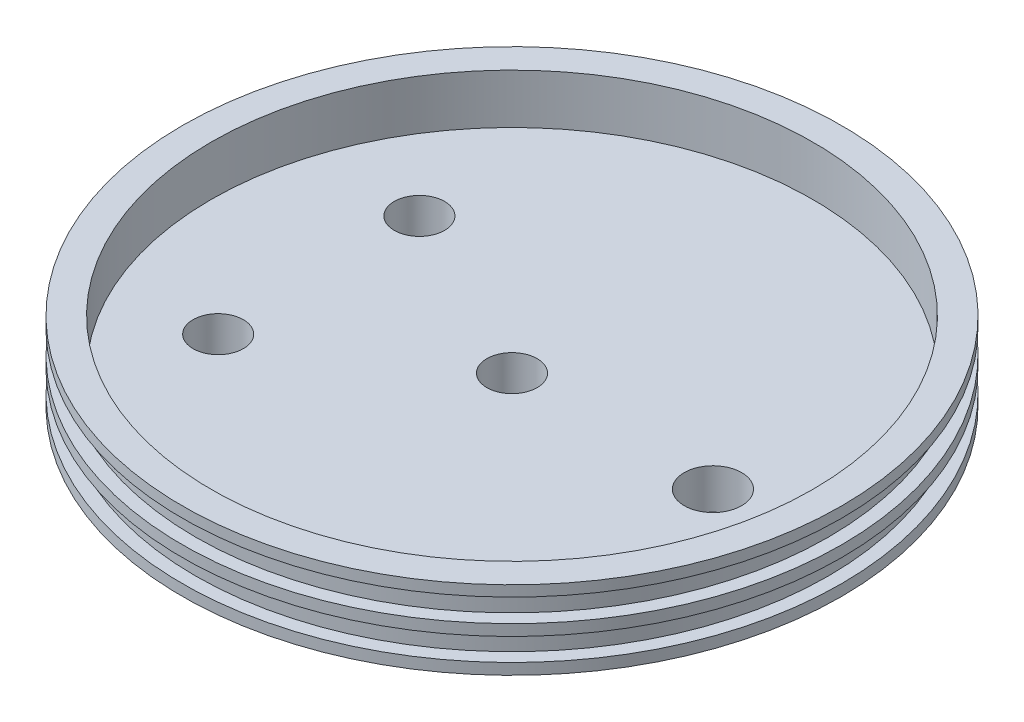
SolidWorks part; units mm, degrees
material "6061-T6 (SS)"
ref_plane "Front Plane" through (0, 0, 0) normal (0, 0, 1) x (1, 0, 0)
ref_plane "Top Plane" through (0, 0, 0) normal (0, 1, 0) x (1, 0, 0)
ref_plane "Right Plane" through (0, 0, 0) normal (1, 0, 0) x (0, 0, -1)
sketch "Sketch1" plane through (0, 0, 0) normal (0, 0, 1) x (1, 0, 0)
  line L0 (0, 48.1922) -> (0, -25.6743) construction
  line L1 (0, 0) -> (72.898, 0)
  line L2 (72.898, 0) -> (72.898, 2.4638)
  line L3 (72.898, 2.4638) -> (69.977, 2.4638)
  line L4 (69.977, 2.4638) -> (69.977, 7.4422)
  line L5 (69.977, 7.4422) -> (72.898, 7.4422)
  line L6 (72.898, 7.4422) -> (72.898, 9.906)
  line L7 (72.898, 9.906) -> (69.977, 9.906)
  line L8 (66.548, 17.3482) -> (66.548, 6.35)
  line L9 (66.548, 6.35) -> (0, 6.35)
  line L10 (0, 6.35) -> (0, 0)
  line L11 (69.977, 9.906) -> (69.977, 14.986)
  line L12 (69.977, 14.986) -> (72.898, 14.986)
  line L13 (72.898, 14.986) -> (72.898, 17.3482)
  line L14 (72.898, 17.3482) -> (66.548, 17.3482)
  dimension "D1" = 145.796
  dimension "D2" = 4.9784
  dimension "D3" = 2.921
  dimension "D4" = 9.906
  dimension "D5" = 6.35
  dimension "D6" = 6.35
  dimension "D7" = 5.08
  dimension "D8" = 9.906
revolve "Revolve1" add sketch "Sketch1" angle 360 about L0
sketch "Sketch6" plane through (0, 0, 0) normal (0, -1, 0) x (1, 0, 0)
  circle A0 centre (0, 0) radius 66.04
  dimension "D1" = 132.08
extrude "Boss-Extrude1" add sketch "Sketch6" along normal blind 2.54
hole_wizard "Pipe Tap Drill for 1/4 Tap - GN2" positions "Sketch2" profile "Sketch3" hole size "1/4" standard "ANSI Inch" end condition through all
sketch "Sketch2" plane through (0, 6.35, 0) normal (0, 1, 0) x (1, 0, 0)
  point P4 (0, 0)
  dimension "D1" = 0
sketch "Sketch3" plane through (0, 6.35, 0) normal (1, 0, 0) x (0, 0, 1)
  line L0 (0, 0) -> (0, 8.89)
  line L1 (0, 8.89) -> (5.5626, 8.89)
  line L2 (5.5626, 8.89) -> (5.5626, 0)
  line L5 (5.5626, 0) -> (0, 0)
  line L11 (0, -6.35) -> (0, 107.95) construction
  dimension "Thru Hole Dia." = 11.1252
  dimension "Thru Hole Depth" = 8.89
fillet "CNC ID Fillet" [suppressed] radius 0.1778
fillet "CNC OD Fillet" [suppressed] radius 0.127
chamfer "CNC Chamfers" [suppressed] distance 0.254 angle 45
fillet "CNC Bore Fillet" [suppressed] radius 0.254
sketch "Sketch7" plane through (0, -2.54, 0) normal (0, -1, 0) x (-1, 0, 0)
  circle A0 centre (-44.45, 0) radius 6.35
  dimension "D1" = 12.7
  dimension "D2" = 44.45
extrude "Cut-Extrude1-Siphon" cut sketch "Sketch7" against normal through all
hole_wizard "Pipe Tap Drill for 1/4 Tap - Relief Valve" positions "Sketch13" profile "Sketch14" hole size "1/4" standard "ANSI Inch" end condition through all
sketch "Sketch13" plane through (0, -2.54, 0) normal (0, -1, 0) x (-1, 0, 0)
  point P4 (40.358, 19.8786)
sketch "Sketch14" plane through (-40.358, -2.54, -19.8786) normal (1, 0, 0) x (0, 0, -1)
  line L0 (0, 0) -> (0, 19.8882)
  line L1 (0, 19.8882) -> (5.5626, 19.8882)
  line L2 (5.5626, 19.8882) -> (5.5626, 0)
  line L5 (5.5626, 0) -> (0, 0)
  line L11 (0, -6.35) -> (0, 107.95) construction
  dimension "Thru Hole Dia." = 11.1252
  dimension "Thru Hole Depth" = 19.8882
hole_wizard "Pipe Tap Drill for 1/4 Tap - Vent Valve" positions "Sketch15" profile "Sketch16" hole size "1/4" standard "ANSI Inch" end condition through all
sketch "Sketch15" plane through (0, -2.54, 0) normal (0, -1, 0) x (-1, 0, 0)
  point P4 (39.9614, -25.0312)
sketch "Sketch16" plane through (-39.9614, -2.54, 25.0312) normal (1, 0, 0) x (0, 0, -1)
  line L0 (0, 0) -> (0, 19.8882)
  line L1 (0, 19.8882) -> (5.5626, 19.8882)
  line L2 (5.5626, 19.8882) -> (5.5626, 0)
  line L5 (5.5626, 0) -> (0, 0)
  line L11 (0, -6.35) -> (0, 107.95) construction
  dimension "Thru Hole Dia." = 11.1252
  dimension "Thru Hole Depth" = 19.8882
